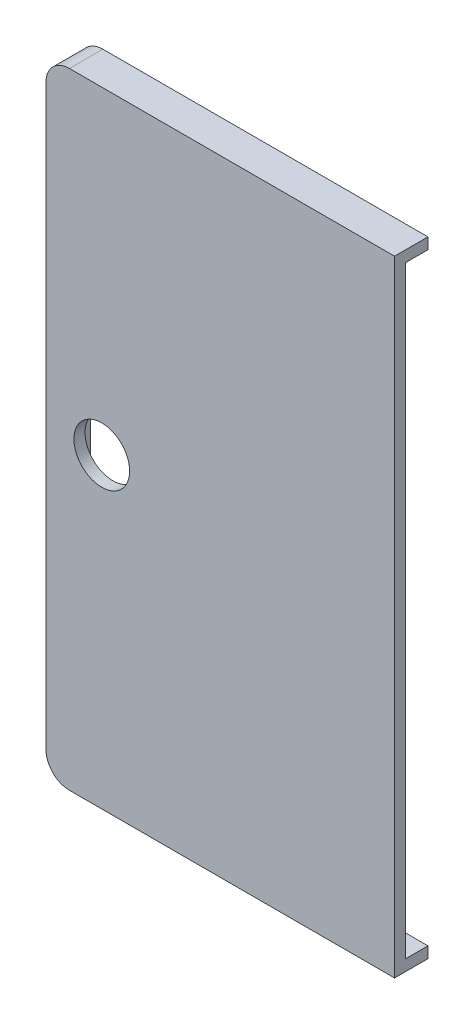
SolidWorks part; units mm, degrees
ref_plane "Front Plane" through (0, 0, 0) normal (0, 0, 1) x (1, 0, 0)
ref_plane "Top Plane" through (0, 0, 0) normal (0, 1, 0) x (1, 0, 0)
ref_plane "Right Plane" through (0, 0, 0) normal (1, 0, 0) x (0, 0, -1)
sketch "Sketch1" plane through (0, 0, 0) normal (0, 0, 1) x (1, 0, 0)
  line L4 (657.3112, -1230.231) -> (657.3112, -1334.011)
  line L5 (661.5112, -1338.211) -> (719.8512, -1338.211)
  line L7 (719.8512, -1226.031) -> (661.5112, -1226.031)
  line L8 (659.3112, -1230.231) -> (659.3112, -1334.011)
  line L9 (661.5112, -1336.211) -> (769.8512, -1336.211)
  line L10 (772.0512, -1334.011) -> (772.0512, -1230.231)
  line L11 (769.8512, -1228.031) -> (661.5112, -1228.031)
  line L12 (659.3112, -1230.231) -> (659.3112, -1334.011)
  line L13 (661.5112, -1336.211) -> (719.8512, -1336.211)
  line L15 (719.8512, -1228.031) -> (661.5112, -1228.031)
  line L16 (719.8512, -1327.661) -> (719.8512, -1261.621) construction
  line L17 (719.8512, -1327.661) -> (719.8512, -1261.621)
  line L18 (719.8512, -1261.621) -> (719.8512, -1226.031)
  line L19 (719.8512, -1327.661) -> (719.8512, -1338.211)
  line L20 (769.8512, -1226.031) -> (661.5112, -1226.031) construction
  line L21 (769.8512, -1228.031) -> (661.5112, -1228.031) construction
  line L22 (661.5112, -1336.211) -> (769.8512, -1336.211) construction
  line L23 (661.5112, -1338.211) -> (769.8512, -1338.211) construction
  line L24 (772.0512, -1334.011) -> (772.0512, -1230.231) construction
  line L25 (774.0512, -1334.011) -> (774.0512, -1230.231) construction
  arc A4 (657.3112, -1334.011) -> (661.5112, -1338.211) centre (661.5112, -1334.011) ccw
  arc A7 (661.5112, -1226.031) -> (657.3112, -1230.231) centre (661.5112, -1230.231) ccw
  arc A8 (659.3112, -1334.011) -> (661.5112, -1336.211) centre (661.5112, -1334.011) ccw
  arc A9 (769.8512, -1336.211) -> (772.0512, -1334.011) centre (769.8512, -1334.011) ccw
  arc A10 (772.0512, -1230.231) -> (769.8512, -1228.031) centre (769.8512, -1230.231) ccw
  arc A11 (661.5112, -1228.031) -> (659.3112, -1230.231) centre (661.5112, -1230.231) ccw
  arc A12 (659.3112, -1334.011) -> (661.5112, -1336.211) centre (661.5112, -1334.011) ccw
  arc A15 (661.5112, -1228.031) -> (659.3112, -1230.231) centre (661.5112, -1230.231) ccw
  arc A20 (774.0512, -1230.231) -> (769.8512, -1226.031) centre (769.8512, -1230.231) ccw construction
  arc A21 (772.0512, -1230.231) -> (769.8512, -1228.031) centre (769.8512, -1230.231) ccw construction
  arc A22 (769.8512, -1338.211) -> (774.0512, -1334.011) centre (769.8512, -1334.011) ccw construction
  arc A23 (769.8512, -1336.211) -> (772.0512, -1334.011) centre (769.8512, -1334.011) ccw construction
  dimension "D2" = 2
extrude "Boss-Extrude1" add sketch "Sketch1" along normal blind 2 contours A15 L15 L18 L7 A7 L4 A4 L5 L19 L13 A12 L12 | L15 A15 L12 A12 L13 L19 L17 L18 region at (659.4496, -1228.1693, 0) region at (689.5907, -1282.121, 0)
extrude "Boss-Extrude2" add sketch "Sketch1<3>" against normal blind 4 contours A15 L15 L18 L7 A7 L4 A4 L5 L19 L13 A12 L12 region at (659.4496, -1228.1693, 0)
sketch "Sketch1<3>" plane through (0, 0, 0) normal (0, 0, 1) x (1, 0, 0) same geometry as "Sketch1"
sketch "Sketch2" plane through (0, 0, 2) normal (0, 0, 1) x (1, 0, 0)
  line L0 (657.3112, -1283.211) -> (667.3112, -1283.211)
  line L1 (657.3112, -1230.231) -> (657.3112, -1334.011) construction
  line L2 (667.3112, -1283.211) -> (667.3112, -1338.211)
  line L3 (661.5112, -1338.211) -> (719.8512, -1338.211) construction
  circle A0 centre (667.3112, -1283.211) radius 5
  dimension "D3" = 10
  dimension "D1" = 55
  dimension "D2" = 10
extrude "Cut-Extrude1" cut sketch "Sketch2" against normal up to surface (2 mm away) contours L2 A0 L0 | L0 A0 L2 region at (668.0186, -1282.5036, 2) region at (665.1892, -1285.333, 2) up to face at (680.0727, -1282.121, 0)
equation "\"C\"=0.2"
equation "\"D1@Sketch1\"=\"C\""
equation "\"T\"=2"
equation "\"D2@Sketch1\"=\"T\""
equation "\"D1@Boss-Extrude1\"=\"T\""
equation "\"HANG\"=4"
equation "\"D2@Boss-Extrude1\"=\"HANG\""
equation "\"D1@Boss-Extrude2\"=\"HANG\""
equation "\"OFF1\"=55"
equation "\"OFF2\"=10"
equation "\"D2@Sketch2\"=\"OFF2\""
equation "\"HOLED\"= 10"
equation "\"D3@Sketch2\"=\"HOLED\""
equation "\"D1@Sketch2\"=\"OFF1\""
